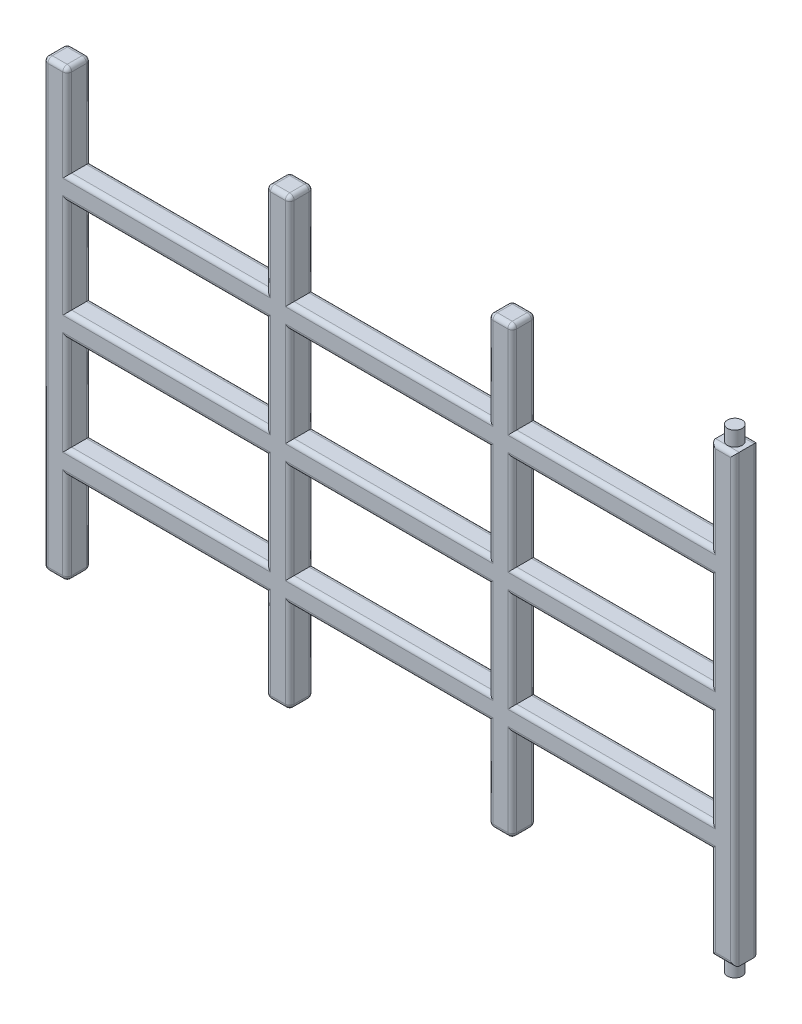
SolidWorks part; units mm, degrees
ref_plane "前视基准面" through (0, 0, 0) normal (0, 0, 1) x (1, 0, 0)
ref_plane "上视基准面" through (0, 0, 0) normal (0, 1, 0) x (1, 0, 0)
ref_plane "右视基准面" through (0, 0, 0) normal (1, 0, 0) x (0, 0, -1)
sketch "草图1" plane through (0, 0, 0) normal (0, 0, 1) x (1, 0, 0)
  line L0 (75, 150) -> (75, 0)
  line L1 (0, 150) -> (8, 150)
  line L2 (0, 150) -> (0, 0)
  line L3 (0, 0) -> (8, 0)
  line L4 (8, 150) -> (8, 0)
  line L5 (75, 150) -> (83, 150)
  line L6 (83, 150) -> (83, 0)
  line L7 (75, 0) -> (83, 0)
  line L8 (150, 150) -> (150, 0)
  line L9 (150, 150) -> (158, 150)
  line L10 (158, 150) -> (158, 0)
  line L11 (150, 0) -> (158, 0)
  line L12 (225, 150) -> (225, 0)
  line L13 (225, 150) -> (233, 150)
  line L14 (233, 150) -> (233, 0)
  line L15 (225, 0) -> (233, 0)
  line L16 (0, 79) -> (0, 71)
  line L17 (0, 119) -> (233, 119)
  line L18 (0, 119) -> (0, 111)
  line L19 (0, 111) -> (233, 111)
  line L20 (233, 119) -> (233, 111)
  line L21 (233, 79) -> (233, 71)
  line L22 (0, 71) -> (233, 71)
  line L23 (0, 79) -> (233, 79)
  line L24 (0, 39) -> (0, 31)
  line L25 (233, 39) -> (233, 31)
  line L26 (0, 31) -> (233, 31)
  line L27 (0, 39) -> (233, 39)
  point P23 (0, 75)
  point P30 (0, 75)
  dimension "D1" = 8
  dimension "D2" = 150
  dimension "D3" = 4
  dimension "D4" = 75
  dimension "D5" = 8
  dimension "D7" = 40
  dimension "D6" = 3
extrude "凸台-拉伸1" add sketch "草图1" along normal blind 8 contours L2 L17 L4 L1 | L4 L19 L0 L17 | L2 L19 L4 L17 | L2 L23 L4 L19 | L23 L4 L22 L0 | L2 L27 L4 L22 | L23 L2 L22 L4 | L27 L2 L26 L4 | L26 L2 L3 L4 | L27 L4 L26 L0 | L27 L0 L26 L6 | L26 L0 L7 L6 | L0 L27 L6 L22 | L23 L0 L22 L6 | L0 L23 L6 L19 | L0 L19 L6 L17 | L0 L17 L6 L5 | L6 L19 L8 L17 | L23 L6 L22 L8 | L27 L6 L26 L8 | L26 L8 L11 L10 | L27 L8 L26 L10 | L8 L27 L10 L22 | L23 L8 L22 L10 | L8 L23 L10 L19 | L8 L19 L10 L17 | L8 L17 L10 L9 | L10 L19 L12 L17 | L23 L10 L22 L12 | L27 L10 L26 L12 | L26 L12 L15 L14 | L27 L12 L26 L14 | L12 L27 L14 L22 | L23 L12 L22 L14 | L12 L23 L14 L19 | L12 L19 L14 L17 | L12 L17 L14 L13 region at (79, 134.5, 0) region at (79, 115, 0) region at (41.5, 115, 0) region at (79, 95, 0) region at (4, 134.5, 0) region at (4, 115, 0) region at (116.5, 115, 0) region at (79, 75, 0) region at (41.5, 75, 0) region at (4, 95, 0) region at (154, 115, 0) region at (154, 134.5, 0) region at (79, 55, 0) region at (4, 75, 0) region at (116.5, 75, 0) region at (154, 95, 0) region at (191.5, 115, 0) region at (79, 35, 0) region at (41.5, 35, 0) region at (4, 55, 0) region at (154, 75, 0) region at (229, 115, 0) region at (229, 134.5, 0) region at (79, 15.5, 0) region at (4, 35, 0) region at (116.5, 35, 0) region at (154, 55, 0) region at (191.5, 75, 0) region at (229, 95, 0) region at (4, 15.5, 0) region at (154, 35, 0) region at (229, 75, 0) region at (154, 15.5, 0) region at (191.5, 35, 0) region at (229, 55, 0) region at (229, 35, 0) region at (229, 15.5, 0)
sketch "草图2" plane through (0, 150, 0) normal (0, 1, 0) x (1, 0, 0)
  line L0 (233, 0) -> (225, 0) construction
  line L1 (225, 0) -> (225, -8) construction
  line L2 (225, -8) -> (233, -8) construction
  line L3 (233, -8) -> (233, 0) construction
  line L4 (158, 0) -> (150, 0) construction
  line L5 (150, 0) -> (150, -8) construction
  line L6 (150, -8) -> (158, -8) construction
  line L7 (158, -8) -> (158, 0) construction
  line L8 (83, 0) -> (75, 0) construction
  line L9 (75, 0) -> (75, -8) construction
  line L10 (75, -8) -> (83, -8) construction
  line L11 (83, -8) -> (83, 0) construction
  line L12 (8, 0) -> (0, 0) construction
  line L13 (0, 0) -> (0, -8) construction
  line L14 (0, -8) -> (8, -8) construction
  line L15 (8, -8) -> (8, 0) construction
  line L16 (233, 0) -> (225, 0)
  line L17 (225, 0) -> (225, -8)
  line L18 (225, -8) -> (233, -8)
  line L19 (233, -8) -> (233, 0)
  line L20 (158, 0) -> (150, 0)
  line L21 (150, 0) -> (150, -8)
  line L22 (150, -8) -> (158, -8)
  line L23 (158, -8) -> (158, 0)
  line L24 (83, 0) -> (75, 0)
  line L25 (75, 0) -> (75, -8)
  line L26 (75, -8) -> (83, -8)
  line L27 (83, -8) -> (83, 0)
  line L28 (8, 0) -> (0, 0)
  line L29 (0, 0) -> (0, -8)
  line L30 (0, -8) -> (8, -8)
  line L31 (8, -8) -> (8, 0)
  circle A0 centre (4, -4) radius 2.475
  circle A1 centre (79, -4) radius 2.475
  circle A2 centre (154, -4) radius 2.475
  circle A3 centre (229, -4) radius 2.475
  point P6 (0, 0)
  point P7 (4, 0)
  point P10 (0, -4)
  point P12 (0, 0)
  point P26 (0, 0)
  dimension "D1" = 4.95
  dimension "D3" = 75
  dimension "D2" = 4
sketch "草图3" plane through (0, 0, 0) normal (0, -1, 0) x (1, 0, 0)
  line L0 (-0.9937, 4) -> (8.6298, 4) construction
  line L1 (4, 8.4977) -> (4, -0.4756) construction
  line L4 (0, 0) -> (8, 0)
  line L5 (8, 0) -> (8, 8)
  line L6 (8, 8) -> (0, 8)
  line L7 (0, 8) -> (0, 0)
  line L8 (0, 0) -> (8, 0)
  line L9 (8, 0) -> (8, 8)
  line L10 (8, 8) -> (0, 8)
  line L11 (0, 8) -> (0, 0)
  circle A0 centre (4, 4) radius 2.475
  circle A1 centre (79, 4) radius 2.475
  circle A2 centre (154, 4) radius 2.475
  circle A3 centre (229, 4) radius 2.475
  point P6 (0, 4)
  point P9 (4, 8)
  dimension "D2" = 4.95
  dimension "D3" = 4
  dimension "D4" = 75
  dimension "D1" = 0
sketch "草图4" plane through (0, 0, 0) normal (0, -1, 0) x (1, 0, 0)
  line L0 (0, 8) -> (8, 8) construction
  line L1 (0, 8) -> (0, 0) construction
  circle A0 centre (4, 4) radius 2.525
  circle A1 centre (229, 4) radius 2.525
  dimension "D1" = 5.05
  dimension "D4" = 2
  dimension "D2" = 4
  dimension "D3" = 4
fillet "圆角3" radius 1.5 104 edges at (158, 15.5, 8) (154, 0, 8) (150, 15.5, 8) (116.5, 31, 8) (83, 15.5, 8) (79, 0, 8) (75, 15.5, 8) (41.5, 31, 8) (8, 15.5, 8) (4, 0, 8) (0, 75, 8) (4, 150, 8) (8, 134.5, 8) (41.5, 119, 8) (75, 134.5, 8) (79, 150, 8) (83, 134.5, 8) (116.5, 119, 8) (150, 134.5, 8) (154, 150, 8) (158, 134.5, 8) (191.5, 119, 8) (225, 134.5, 8) (229, 150, 8) (233, 75, 8) (229, 0, 8) (225, 15.5, 8) (191.5, 31, 8) (116.5, 39, 0) (83, 55, 0) (116.5, 71, 0) (150, 55, 0) (116.5, 79, 0) (83, 95, 0) (116.5, 111, 0) (150, 95, 0) (41.5, 79, 0) (8, 95, 0) (41.5, 111, 0) (75, 95, 0) (41.5, 39, 0) (8, 55, 0) (41.5, 71, 0) (75, 55, 0) (225, 15.5, 0) (229, 0, 0) (233, 75, 0) (229, 150, 0) (225, 134.5, 0) (191.5, 119, 0) (158, 134.5, 0) (154, 150, 0) (150, 134.5, 0) (116.5, 119, 0) (83, 134.5, 0) (79, 150, 0) (75, 134.5, 0) (41.5, 119, 0) (8, 134.5, 0) (4, 150, 0) (0, 75, 0) (4, 0, 0) (8, 15.5, 0) (41.5, 31, 0) (75, 15.5, 0) (79, 0, 0) (83, 15.5, 0) (116.5, 31, 0) (150, 15.5, 0) (154, 0, 0) (158, 15.5, 0) (191.5, 31, 0) (191.5, 79, 0) (158, 95, 0) (191.5, 111, 0) (225, 95, 0) (191.5, 39, 0) (158, 55, 0) (191.5, 71, 0) (225, 55, 0) (41.5, 111, 8) (8, 95, 8) (41.5, 79, 8) (75, 95, 8) (116.5, 111, 8) (83, 95, 8) (116.5, 79, 8) (150, 95, 8) (41.5, 71, 8) (8, 55, 8) (41.5, 39, 8) (75, 55, 8) (191.5, 111, 8) (158, 95, 8) (191.5, 79, 8) (225, 95, 8) (116.5, 71, 8) (83, 55, 8) (116.5, 39, 8) (150, 55, 8) (191.5, 71, 8) (158, 55, 8) (191.5, 39, 8) (225, 55, 8)
extrude "凸台-拉伸5" add sketch "草图2" along normal blind 4.95 contours A3 region at (229, 150, 4)
extrude "凸台-拉伸6" add sketch "草图3" along normal blind 4.95 contours A3
fillet "圆角4" radius 1.5 36 edges at (150.4393, 0.4393, 7.5607) (150.4393, 0.4393, 0.4393) (157.5607, 0.4393, 7.5607) (157.5607, 0.4393, 0.4393) (75.4393, 0.4393, 7.5607) (75.4393, 0.4393, 0.4393) (82.5607, 0.4393, 7.5607) (82.5607, 0.4393, 0.4393) (7.5607, 0.4393, 7.5607) (7.5607, 0.4393, 0.4393) (0.4393, 0.4393, 7.5607) (0.4393, 0.4393, 0.4393) (0.4393, 149.5607, 7.5607) (0.4393, 149.5607, 0.4393) (7.5607, 149.5607, 7.5607) (7.5607, 149.5607, 0.4393) (157.5607, 149.5607, 7.5607) (157.5607, 149.5607, 0.4393) (150.4393, 149.5607, 7.5607) (150.4393, 149.5607, 0.4393) (75.4393, 149.5607, 7.5607) (75.4393, 149.5607, 0.4393) (82.5607, 149.5607, 7.5607) (82.5607, 149.5607, 0.4393) (150, 0, 4) (158, 0, 4) (75, 0, 4) (83, 0, 4) (8, 0, 4) (0, 0, 4) (0, 150, 4) (8, 150, 4) (158, 150, 4) (150, 150, 4) (75, 150, 4) (83, 150, 4)
